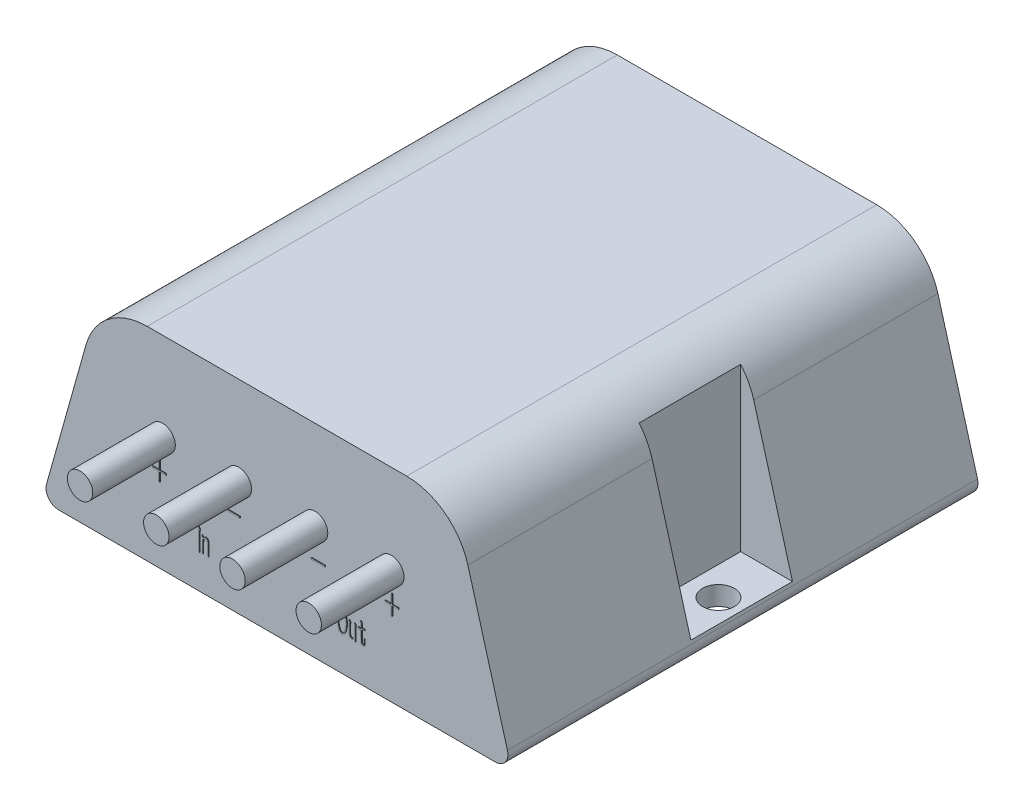
SolidWorks part; units mm, degrees
ref_plane "前视基准面" through (0, 0, 0) normal (0, 0, 1) x (1, 0, 0)
ref_plane "上视基准面" through (0, 0, 0) normal (0, 1, 0) x (1, 0, 0)
ref_plane "右视基准面" through (0, 0, 0) normal (1, 0, 0) x (0, 0, -1)
sketch "草图1" plane through (0, 0, 0) normal (0, 1, 0) x (1, 0, 0)
  line L1 (37, -37) -> (-37, -37)
  line L2 (37, -37) -> (37, 37)
  line L3 (37, 37) -> (-37, 37)
  line L4 (-37, -37) -> (-37, 37)
  line L5 (37, -37) -> (-37, 37) construction
  line L6 (37, 37) -> (-37, -37) construction
  point P0 (0, 0)
  dimension "D1" = 74
  dimension "D2" = 74
ref_plane "基准面1" through (0, 32, 0) normal (0, 1, 0) x (1, 0, 0)
sketch "草图2" plane through (0, 32, 0) normal (0, 1, 0) x (1, 0, 0)
  line L0 (37, 37) -> (-37, 37) construction
  line L1 (28, -37) -> (-28, -37)
  line L2 (28, -37) -> (28, 37)
  line L3 (28, 37) -> (-28, 37)
  line L4 (-28, -37) -> (-28, 37)
  line L5 (28, -37) -> (-28, 37) construction
  line L6 (28, 37) -> (-28, -37) construction
  point P0 (0, 0)
  dimension "D1" = 56
loft "放样1" add profiles "草图1", "草图2"
sketch "草图3" plane through (0, 32, 0) normal (0, 1, 0) x (1, 0, 0)
  line L0 (0, 0) -> (0, 13.9223) construction
  circle A0 centre (-32.5, 0) radius 2.5
  circle A1 centre (32.5, 0) radius 2.5
  dimension "D1" = 5
  dimension "D2" = 65
extrude "切除-拉伸1" cut sketch "草图3" against normal through all
sketch "草图4" plane through (0, 32, 0) normal (0, 1, 0) x (1, 0, 0)
  line L0 (-37, 37) -> (-37, -37) construction
  line L1 (-28, -8) -> (-37, -8)
  line L2 (-28, -8) -> (-28, 8)
  line L3 (-28, 8) -> (-37, 8)
  line L4 (-37, -8) -> (-37, 8)
  line L5 (-28, -8) -> (-37, 8) construction
  line L6 (-28, 8) -> (-37, -8) construction
  line L7 (0, 0) -> (0, 11.6305) construction
  line L8 (28, 8) -> (37, -8) construction
  line L9 (28, -8) -> (37, 8) construction
  line L10 (37, -8) -> (37, 8)
  line L11 (28, 8) -> (37, 8)
  line L12 (28, -8) -> (28, 8)
  line L13 (28, -8) -> (37, -8)
  point P0 (-32.5, 0)
  point P15 (32.5, 0)
  dimension "D1" = 16
extrude "切除-拉伸2" cut sketch "草图4" against normal offset from surface (29 mm away) 3 up to face at (32.5, 0, 2.5)
sketch "草图5" plane through (0, 0, 37) normal (0, 0, 1) x (1, 0, 0)
  line L0 (0, 0) -> (0, 32) construction
  line L1 (40.7001, 32) -> (-40.7001, 32) construction
  line L2 (-37, 0) -> (37, 0) construction
  circle A0 centre (-6, 18) radius 2
  circle A1 centre (-18, 18) radius 2
  circle A2 centre (18, 18) radius 2
  circle A3 centre (6, 18) radius 2
  dimension "D3" = 4
  dimension "D4" = 18
  dimension "D1" = 12
  dimension "D2" = 36
extrude "凸台-拉伸1" add sketch "草图5" along normal blind 13
sketch "草图6" plane through (0, 0, 0) normal (0, 0, 1) x (1, 0, 0)
  text T0 "+     -      -     +\r\n    In           Out"
extrude "凸台-拉伸2" add sketch "草图6" along normal offset from surface (37.1 mm away) 0.1 up to face at (6, 20, 37) offset beyond the face yes
fillet "圆角1" radius 10 2 edges
fillet "圆角2" radius 2 2 edges
